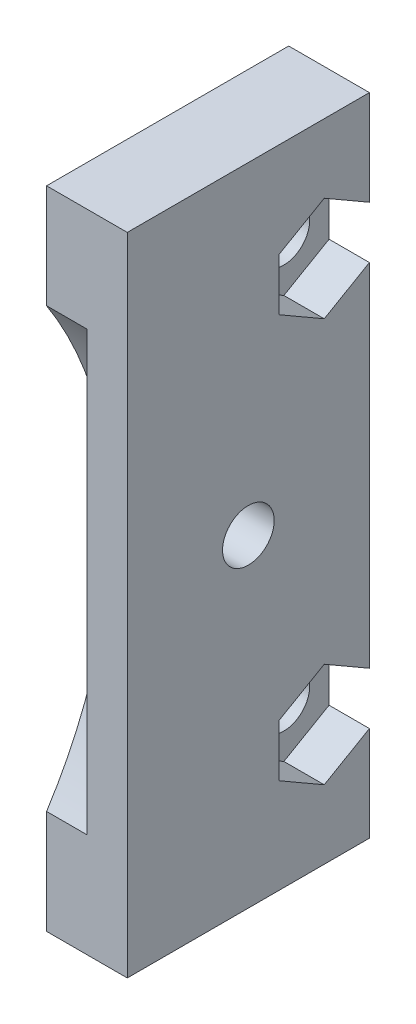
SolidWorks part; units mm, degrees
ref_plane "Front" through (0, 0, 0) normal (0, 0, 1) x (1, 0, 0)
ref_plane "Top" through (0, 0, 0) normal (0, 1, 0) x (1, 0, 0)
ref_plane "Right" through (0, 0, 0) normal (1, 0, 0) x (0, 0, -1)
sketch "Sketch1" plane through (0, 0, 0) normal (1, 0, 0) x (0, 0, -1)
  line L0 (7.5, 40) -> (7.5, 0)
  line L1 (0, 0) -> (15, 0)
  line L2 (0, 0) -> (0, 40)
  line L3 (0, 40) -> (15, 40)
  line L4 (15, 0) -> (15, 40)
  line L5 (12.2, 29.2668) -> (15, 30.8834)
  line L6 (15, 30.8834) -> (15, 34.1166)
  line L7 (15, 34.1166) -> (12.2, 35.7332)
  line L8 (12.2, 35.7332) -> (9.4, 34.1166)
  line L9 (9.4, 34.1166) -> (9.4, 30.8834)
  line L10 (9.4, 30.8834) -> (12.2, 29.2668)
  line L11 (12.2, 4.2668) -> (15, 5.8834)
  line L12 (15, 5.8834) -> (15, 9.1166)
  line L13 (15, 9.1166) -> (12.2, 10.7332)
  line L14 (12.2, 10.7332) -> (9.4, 9.1166)
  line L15 (9.4, 9.1166) -> (9.4, 5.8834)
  line L16 (9.4, 5.8834) -> (12.2, 4.2668)
  circle A0 centre (12.2, 32.5) radius 2.8 construction
  circle A1 centre (12.2, 7.5) radius 2.8 construction
  circle A2 centre (7.5, 8) radius 1.6
  circle A3 centre (7.5, 20) radius 1.6
  circle A4 centre (12.2, 32.5) radius 1.6
  circle A5 centre (12.2, 7.5) radius 1.6
  dimension "D3" = 2.8
  dimension "D7" = 20
  dimension "D1" = 15
  dimension "D2" = 40
  dimension "D4" = 2.8
  dimension "D5" = 7.5
  dimension "D6" = 7.5
  dimension "D8" = 8
extrude "Boss-Extrude1" add sketch "Sketch1" along normal blind 2.5 contours A3 L0 L3 L2 L1 A2 | A3 L0 A2 L1 L4 L11 L16 L15 L14 L13 L5 L10 L9 L8 L7 L3 | L0 A2 | L0 A2 region at (0, 20.2031, -11.1368) region at (0, 20.1653, -3.6654) region at (0, 8, -8.1791) region at (0, 8, -6.8209)
extrude "Boss-Extrude2" add sketch "Sketch1<3>" against normal blind 2.5 contours A3 L0 A2 L1 L4 L11 L16 L15 L14 L13 L5 L10 L9 L8 L7 L3 | A3 L0 L3 L2 L1 A2 | L15 L16 L11 L4 L13 L14 A5 | L9 L10 L5 L4 L7 L8 A4 | A2 region at (0, 20.2031, -11.1368) region at (0, 20.1653, -3.6654) region at (0, 32.5, -14.9145) region at (0, 7.5, -14.9145)
sketch "Sketch1<3>" plane through (0, 0, 0) normal (1, 0, 0) x (0, 0, -1) same geometry as "Sketch1"
sketch "Sketch2" plane through (-2.5, 0, 0) normal (-1, 0, 0) x (0, 0, 1)
  circle A0 centre (-12.2, 7.5) radius 1.6
  circle A1 centre (-12.2, 32.5) radius 1.6
extrude "Extrude-Thin1" add sketch "Sketch2" along normal blind 1 thin thin type one direction wall 1
sketch "Sketch3" plane through (-2.5, 0, 0) normal (-1, 0, 0) x (0, 0, 1)
  line L0 (-7.5, 20) -> (21, 20)
  circle A0 centre (21, 20) radius 25
  line M3 (0, 0) -> (0, 40)
  dimension "D1" = 28.5
extrude "Cut-Extrude1" cut sketch "Sketch3" against normal blind 2.5 contours L0 A0 M3 | A0 L0 M3 region at (-2.5, 25.1458, -1.6115) region at (-2.5, 14.8542, -1.6115)
